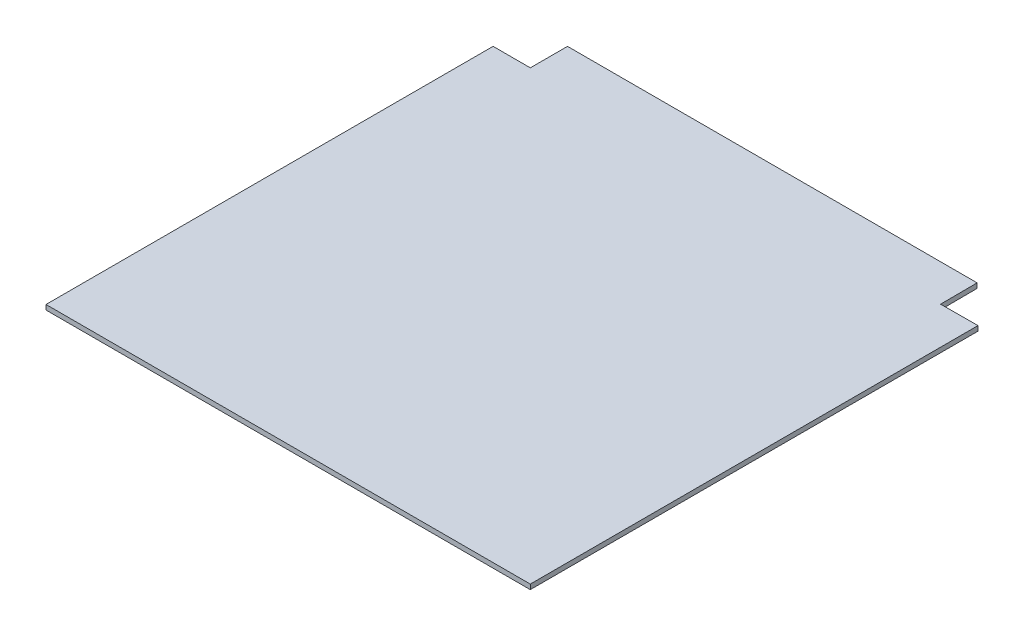
SolidWorks part; units mm, degrees
ref_plane "Front Plane" through (0, 0, 0) normal (0, 0, 1) x (1, 0, 0)
ref_plane "Top Plane" through (0, 0, 0) normal (0, 1, 0) x (1, 0, 0)
ref_plane "Right Plane" through (0, 0, 0) normal (1, 0, 0) x (0, 0, -1)
sketch "Sketch1" plane through (0, 0, 0) normal (0, 1, 0) x (1, 0, 0)
  line L0 (-524.3738, 370.7453) -> (-446.7628, 370.7453)
  line L5 (-446.7628, 447.3859) -> (397.5564, 447.3859)
  line L6 (-523.4951, 370.7453) -> (-523.4951, -550.8568)
  line L7 (-523.4951, -550.8568) -> (474.7475, -550.8568)
  line L8 (474.7475, 372.0134) -> (474.7475, -550.8568)
  line L9 (-446.7628, 370.7453) -> (-446.7628, 447.3859)
  line L10 (474.7475, 372.0134) -> (397.9303, 371.6342)
  line L11 (397.9303, 371.6342) -> (397.5564, 447.3859)
extrude "Boss-Extrude1" add sketch "Sketch1" along normal blind 10 contours L10 L11 L5 L9 L0 L6 L7 L8 region at (-24.3437, 0, 57.2132)
